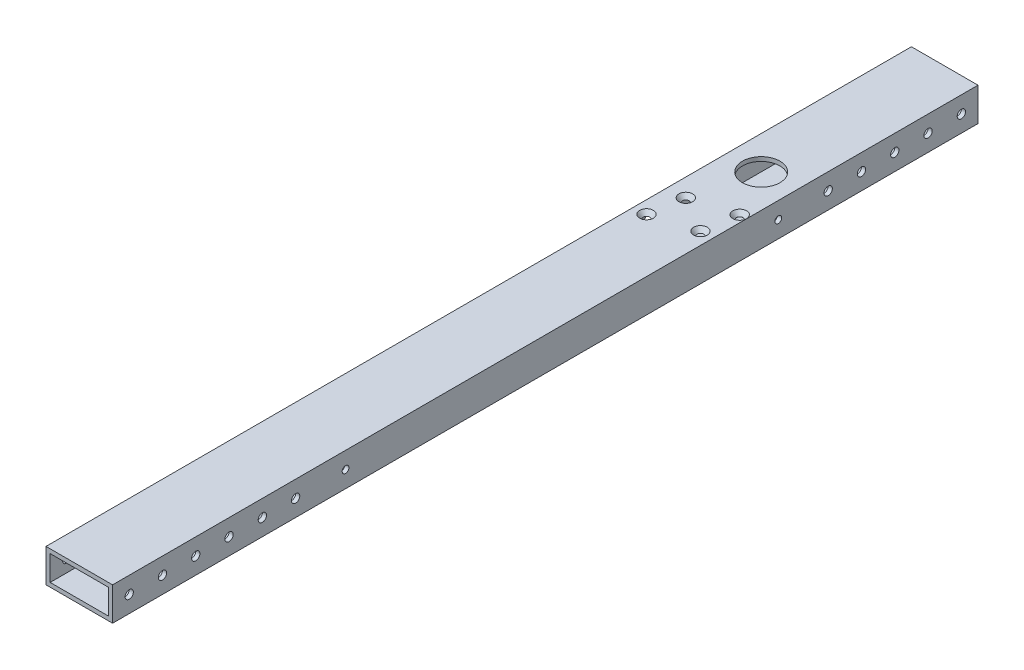
SolidWorks part; units mm, degrees
material "6061 Alloy"
ref_plane "Front Plane" through (0, 0, 0) normal (0, 0, 1) x (1, 0, 0)
ref_plane "Top Plane" through (0, 0, 0) normal (0, 1, 0) x (1, 0, 0)
ref_plane "Right Plane" through (0, 0, 0) normal (1, 0, 0) x (0, 0, -1)
sketch "Sketch1" plane through (0, 0, 0) normal (0, 0, 1) x (1, 0, 0)
  line L0 (-22.225, 9.525) -> (22.225, 9.525)
  line L2 (-25.4, 12.7) -> (25.4, 12.7)
  line L3 (-25.4, 12.7) -> (-25.4, -12.7)
  line L4 (-25.4, -12.7) -> (25.4, -12.7)
  line L5 (25.4, 12.7) -> (25.4, -12.7)
  line L10 (22.225, 9.525) -> (22.225, -9.525)
  line L11 (-22.225, -9.525) -> (22.225, -9.525)
  line L12 (-22.225, 9.525) -> (-22.225, -9.525)
  point P12 (0, 12.7)
  point P14 (25.4, 0)
  dimension "Wall Thickness" = 3.175
  dimension "Outside Width" = 50.8
  dimension "Outside Height" = 25.4
  dimension "Inside Height" = 19.05
  dimension "Inside Width" = 44.45
sketch "Sketch2" plane through (0, 0, 0) normal (1, 0, 0) x (0, 0, -1)
  line L0 (330.2, 0) -> (-330.2, 0)
  point P4 (0, 0)
  point P7 (-330.2, 0)
  point P10 (330.2, 0)
  dimension "Length" = 660.4
sketch "Sketch3" plane through (0, 0, 0) normal (0, 0, 1) x (1, 0, 0)
  line L21 (25.4, 12.7) -> (-25.4, 12.7)
  line L22 (25.4, -12.7) -> (25.4, 12.7)
  line L23 (-25.4, -12.7) -> (25.4, -12.7)
  line L24 (-25.4, 12.7) -> (-25.4, -12.7)
  line L25 (25.4, 12.7) -> (-25.4, 12.7)
  line L26 (25.4, -12.7) -> (25.4, 12.7)
  line L27 (-25.4, -12.7) -> (25.4, -12.7)
  line L28 (-25.4, 12.7) -> (-25.4, -12.7)
  line L29 (22.225, 9.525) -> (-22.225, 9.525)
  line L30 (22.225, -9.525) -> (22.225, 9.525)
  line L31 (-22.225, -9.525) -> (22.225, -9.525)
  line L32 (-22.225, 9.525) -> (-22.225, -9.525)
  line L33 (22.225, 9.525) -> (-22.225, 9.525)
  line L34 (22.225, -9.525) -> (22.225, 9.525)
  line L35 (-22.225, -9.525) -> (22.225, -9.525)
  line L36 (-22.225, 9.525) -> (-22.225, -9.525)
  dimension "D1" = 0
  dimension "D2" = 0
extrude "Boss-Extrude1" add sketch "Sketch3" along normal up to vertex (330.2 mm away) and the other way up to vertex (330.2 mm away) up to point (0, 0, 330.2) other way up to point (0, 0, -330.2)
sketch "Drawing Reference" plane through (0, 0, 0) normal (1, 0, 0) x (0, 0, -1)
  line L0 (-330.2, 0) -> (330.2, 0) construction
  line L1 (0, -12.7) -> (0, 12.7) construction
  line L2 (-330.2, -12.7) -> (330.2, -12.7) construction
  line L5 (-330.2, 12.7) -> (330.2, 12.7) construction
  point P7 (-293.624, 0)
  point P8 (293.624, 0)
  dimension "D1" = 36.576
sketch "Sketch5" plane through (25.4, 0, 0) normal (1, 0, 0) x (0, 0, -1)
  line L2 (-266.7, 0) -> (-241.3, 0)
  line L3 (-241.3, 0) -> (-215.9, 0)
  line L4 (-215.9, 0) -> (-190.5, 0)
  line L5 (-317.5, 0) -> (-330.2, 0)
  line L6 (-330.2, -12.7) -> (-330.2, 12.7) construction
  line L7 (-317.5, 0) -> (-292.1, 0)
  line L8 (-292.1, 0) -> (-266.7, 0)
sketch "Sketch8" plane through (25.4, 0, 0) normal (1, 0, 0) x (0, 0, -1)
  line L0 (330.2, 0) -> (292.1, 0)
  line L1 (330.2, -12.7) -> (330.2, 12.7) construction
  line L2 (292.1, 0) -> (266.7, 0)
  line L3 (266.7, 0) -> (241.3, 0)
  line L4 (241.3, 0) -> (215.9, 0)
  line L5 (330.2, 0) -> (317.5, 0)
hole_wizard "1/4 (0.25) Diameter Hole3" positions "Sketch12" profile "Sketch13" hole size "1/4" standard "ANSI Inch" end condition through all
sketch "Sketch12" plane through (-25.4, 0, 0) normal (-1, 0, 0) x (0, 0, 1)
  point P4 (-317.5, 0)
sketch "Sketch13" plane through (-25.4, 0, -317.5) normal (0, 1, 0) x (0, 0, 1)
  line L0 (0, 0) -> (0, 50.8)
  line L1 (0, 50.8) -> (3.175, 50.8)
  line L2 (3.175, 50.8) -> (3.175, 0)
  line L5 (3.175, 0) -> (0, 0)
  line L11 (0, -6.35) -> (0, 107.95) construction
  dimension "Thru Hole Dia." = 6.35
  dimension "Thru Hole Depth" = 50.8
hole_wizard "1/4 (0.25) Diameter Hole4" positions "Sketch14" profile "Sketch15" hole size "1/4" standard "ANSI Inch" end condition through all
sketch "Sketch14" plane through (-25.4, 0, 0) normal (-1, 0, 0) x (0, 0, 1)
  point P0 (292.1, 0)
  point P3 (317.5, 0)
sketch "Sketch15" plane through (-25.4, 0, 292.1) normal (0, 1, 0) x (0, 0, 1)
  line L0 (0, 0) -> (0, 50.8)
  line L1 (0, 50.8) -> (3.175, 50.8)
  line L2 (3.175, 50.8) -> (3.175, 0)
  line L5 (3.175, 0) -> (0, 0)
  line L11 (0, -6.35) -> (0, 107.95) construction
  dimension "Thru Hole Dia." = 6.35
  dimension "Thru Hole Depth" = 50.8
hole_wizard "1/4 (0.25) Diameter Hole5" positions "Sketch17" profile "Sketch18" hole size "1/4" standard "ANSI Inch" end condition through all
sketch "Sketch17" plane through (25.4, 0, 0) normal (1, 0, 0) x (0, 0, -1)
  point P0 (292.1, 0)
  point P3 (266.7, 0)
sketch "Sketch18" plane through (25.4, 0, -292.1) normal (0, 1, 0) x (0, 0, -1)
  line L0 (0, 0) -> (0, 50.8)
  line L1 (0, 50.8) -> (3.175, 50.8)
  line L2 (3.175, 50.8) -> (3.175, 0)
  line L5 (3.175, 0) -> (0, 0)
  line L11 (0, -6.35) -> (0, 107.95) construction
  dimension "Thru Hole Dia." = 6.35
  dimension "Thru Hole Depth" = 50.8
hole_wizard "1/4 (0.25) Diameter Hole6" positions "Sketch19" profile "Sketch20" hole size "1/4" standard "ANSI Inch" end condition through all
sketch "Sketch19" plane through (25.4, 0, 0) normal (1, 0, 0) x (0, 0, -1)
  point P0 (215.9, 0)
  point P3 (241.3, 0)
sketch "Sketch20" plane through (25.4, 0, -215.9) normal (0, 1, 0) x (0, 0, -1)
  line L0 (0, 0) -> (0, 50.8)
  line L1 (0, 50.8) -> (3.175, 50.8)
  line L2 (3.175, 50.8) -> (3.175, 0)
  line L5 (3.175, 0) -> (0, 0)
  line L11 (0, -6.35) -> (0, 107.95) construction
  dimension "Thru Hole Dia." = 6.35
  dimension "Thru Hole Depth" = 50.8
hole_wizard "1/4 (0.25) Diameter Hole7" positions "Sketch21" profile "Sketch22" hole size "1/4" standard "ANSI Inch" end condition through all
sketch "Sketch21" plane through (25.4, 0, 0) normal (1, 0, 0) x (0, 0, -1)
  point P0 (-190.5, 0)
  point P3 (-215.9, 0)
sketch "Sketch22" plane through (25.4, 0, 190.5) normal (0, 1, 0) x (0, 0, -1)
  line L0 (0, 0) -> (0, 50.8)
  line L1 (0, 50.8) -> (3.175, 50.8)
  line L2 (3.175, 50.8) -> (3.175, 0)
  line L5 (3.175, 0) -> (0, 0)
  line L11 (0, -6.35) -> (0, 107.95) construction
  dimension "Thru Hole Dia." = 6.35
  dimension "Thru Hole Depth" = 50.8
hole_wizard "1/4 (0.25) Diameter Hole8" positions "Sketch23" profile "Sketch24" hole size "1/4" standard "ANSI Inch" end condition through all
sketch "Sketch23" plane through (25.4, 0, 0) normal (1, 0, 0) x (0, 0, -1)
  point P0 (-266.7, 0)
  point P3 (-241.3, 0)
sketch "Sketch24" plane through (25.4, 0, 266.7) normal (0, 1, 0) x (0, 0, -1)
  line L0 (0, 0) -> (0, 50.8)
  line L1 (0, 50.8) -> (3.175, 50.8)
  line L2 (3.175, 50.8) -> (3.175, 0)
  line L5 (3.175, 0) -> (0, 0)
  line L11 (0, -6.35) -> (0, 107.95) construction
  dimension "Thru Hole Dia." = 6.35
  dimension "Thru Hole Depth" = 50.8
sketch "Sketch25" plane through (25.4, 0, 0) normal (1, 0, 0) x (0, 0, -1)
  line L0 (-190.5, 0) -> (-152.4, 0)
  line L1 (215.9, 0) -> (177.8, 0)
hole_wizard "13/64 (0.20313) Diameter Hole1" positions "Sketch26" profile "Sketch27" hole size "13/64" standard "ANSI Inch" end condition through all
sketch "Sketch26" plane through (25.4, 0, 0) normal (1, 0, 0) x (0, 0, -1)
  point P0 (-152.4, 0)
  point P3 (177.8, 0)
sketch "Sketch27" plane through (25.4, 0, 152.4) normal (0, 1, 0) x (0, 0, -1)
  line L0 (0, 0) -> (0, 50.8)
  line L1 (0, 50.8) -> (2.5798, 50.8)
  line L2 (2.5798, 50.8) -> (2.5798, 0)
  line L5 (2.5798, 0) -> (0, 0)
  line L11 (0, -6.35) -> (0, 107.95) construction
  dimension "Thru Hole Dia." = 5.1595
  dimension "Thru Hole Depth" = 50.8
sketch "Sketch28" plane through (-25.4, 0, 0) normal (-1, 0, 0) x (0, 0, 1)
  line L0 (103.1875, 0) -> (77.7875, 0)
  line L1 (-103.1875, 0) -> (-128.5875, 0)
hole_wizard "1/2 (0.5) Diameter Hole1" positions "Sketch29" profile "Sketch30" hole size "1/2" standard "ANSI Inch"
sketch "Sketch29" plane through (-25.4, 0, 0) normal (-1, 0, 0) x (0, 0, 1)
  point P1 (-591.3016, -480.8022)
  point P3 (-103.1875, 0)
  point P6 (77.7875, 0)
  point P9 (103.1875, 0)
  point P13 (-128.5875, 0)
sketch "Sketch30" plane through (-25.4, -480.8022, -591.3016) normal (0, 1, 0) x (0, 0, 1)
  line L0 (0, 0) -> (0, 10.1655)
  line L1 (0, 10.1655) -> (6.35, 6.35)
  line L2 (6.35, 6.35) -> (6.35, 0)
  line L5 (6.35, 0) -> (0, 0)
  line L10 (0, 10.1655) -> (-6.35, 6.35) construction
  line L11 (0, -6.35) -> (0, 107.95) construction
  dimension "Hole Dia." = 12.7
  dimension "Hole Depth" = 6.35
  dimension "Drill Angle" = 118
sketch "Sketch31" plane through (0, -12.7, 0) normal (0, -1, 0) x (1, 0, 0)
  line L0 (-25.4, -190.1646) -> (25.4, -190.1646) construction
  line L1 (-25.4, 330.2) -> (-25.4, -330.2) construction
  line L2 (25.4, 330.2) -> (25.4, -330.2) construction
  line L3 (0, -190.1646) -> (11.7607, -165.3816) construction
  line L4 (-23.2295, -155.017) -> (577.2816, -332.8965) construction
  line L6 (11.7607, -165.3816) -> (10.4583, -164.7635) construction
  circle A0 centre (0, -190.1646) radius 14.2875
  dimension "D2" = 28.575
  dimension "D1" = 27.432
extrude "Cut-Extrude1" cut sketch "Sketch31" against normal through all
sketch "Sketch32" plane through (0, -12.7, 0) normal (0, -1, 0) x (1, 0, 0)
  line L1 (20.1015, -153.6796) -> (15.9895, -127.825) construction
  line L2 (-11.6485, -144.2748) -> (20.1015, -153.6796) construction
  line L3 (-15.7605, -118.4203) -> (15.9895, -127.825) construction
  line L4 (-11.6485, -144.2748) -> (-15.7605, -118.4203) construction
hole_wizard "#10 Clearance Hole1" positions "Sketch33" profile "Sketch34" hole size "#10" standard "ANSI Inch" end condition through all
sketch "Sketch33" plane through (0, -12.7, 0) normal (0, -1, 0) x (-1, 0, 0)
  point P0 (11.6485, 144.2748)
  point P3 (15.7605, 118.4203)
  point P6 (-15.9895, 127.825)
  point P9 (-20.1015, 153.6796)
sketch "Sketch34" plane through (-11.6485, -12.7, -144.2748) normal (1, 0, 0) x (0, 0, -1)
  line L0 (0, 0) -> (0, 25.4)
  line L1 (0, 25.4) -> (5.2197, 25.4)
  line L2 (2.4892, 22.2589) -> (2.4892, 0)
  line L5 (2.4892, 0) -> (0, 0)
  line L7 (5.2197, 25.4) -> (2.4892, 22.2589)
  line L8 (-5.2197, 25.4) -> (-2.4892, 22.2589) construction
  line L11 (0, -6.35) -> (0, 107.95) construction
  dimension "Thru Hole Dia." = 4.9784
  dimension "Thru Hole Depth" = 25.4
  dimension "Far C'Sink Dia." = 10.4394
  dimension "Far C'Sink Angle" = 82
equation "\"D1@Drawing Reference\"=\"Outside Width@Sketch1\" * 0.72"
